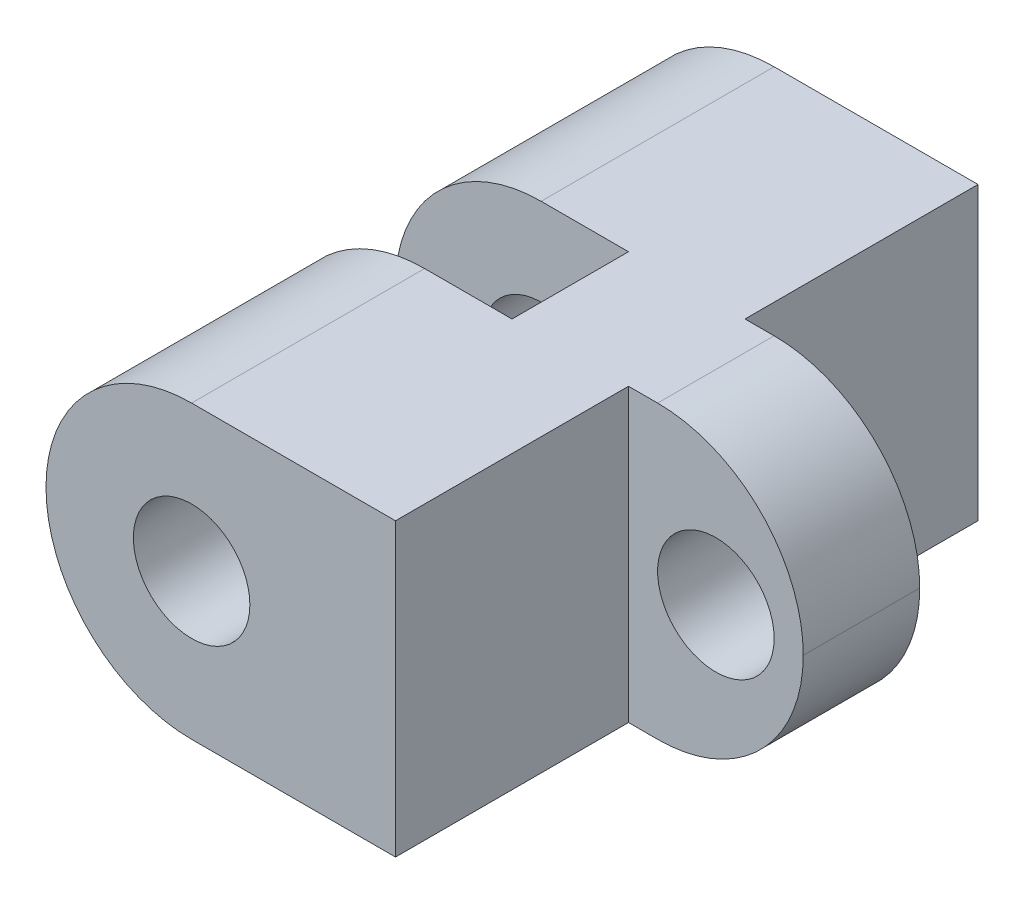
SolidWorks part; units mm, degrees
ref_plane "Alzado" through (0, 0, 0) normal (0, 0, 1) x (1, 0, 0)
ref_plane "Planta" through (0, 0, 0) normal (0, 1, 0) x (1, 0, 0)
ref_plane "Vista lateral" through (0, 0, 0) normal (1, 0, 0) x (0, 0, -1)
sketch "Croquis1" plane through (0, 0, 0) normal (0, 0, 1) x (1, 0, 0)
  line L1 (-45, -25) -> (45, -25)
  line L2 (-45, -25) -> (-45, 25)
  line L3 (-45, 25) -> (45, 25)
  line L4 (45, -25) -> (45, 25)
  line L5 (-45, -25) -> (45, 25) construction
  line L6 (-45, 25) -> (45, -25) construction
  point P0 (0, 0)
extrude "Saliente-Extruir1" add sketch "Croquis1" along normal blind 100
fillet "Redondeo1" radius 25 4 edges at (45, -25, 50) (45, 25, 50) (-45, -25, 50) (-45, 25, 50)
sketch "Croquis2" plane through (0, 0, 0) normal (0, 1, 0) x (1, 0, 0)
  line L1 (45, 0) -> (15, 0)
  line L2 (45, 0) -> (45, -40)
  line L3 (45, -40) -> (15, -40)
  line L4 (15, 0) -> (15, -40)
  line L5 (45, -100) -> (15, -100)
  line L6 (45, -100) -> (45, -60)
  line L7 (45, -60) -> (15, -60)
  line L8 (15, -100) -> (15, -60)
extrude "Cortar-Extruir1" cut sketch "Croquis2" against normal blind 25 and the other way blind 25
sketch "Croquis3" plane through (0, 25, 0) normal (0, 1, 0) x (1, 0, 0)
  line L1 (-45, -100) -> (-45, 0) construction
  line L4 (-45, -40) -> (-5, -40)
  line L5 (-45, -40) -> (-45, -60)
  line L6 (-45, -60) -> (-5, -60)
  line L7 (-5, -40) -> (-5, -60)
  point P0 (0, 0)
sketch "Croquis4" plane through (0, 0, 100) normal (0, 0, 1) x (1, 0, 0)
  circle A0 centre (-20, 0) radius 10
extrude "Cortar-Extruir2" cut sketch "Croquis4" against normal blind 100 contours A0
extrude "Cortar-Extruir3" cut sketch "Croquis3" against normal blind 50 contours L6 L7 L4 L5
sketch "Croquis5" plane through (0, 0, 60) normal (0, 0, 1) x (1, 0, 0)
  circle A0 centre (30, 0) radius 10
extrude "Cortar-Extruir4" cut sketch "Croquis5" against normal blind 20 contours A0
